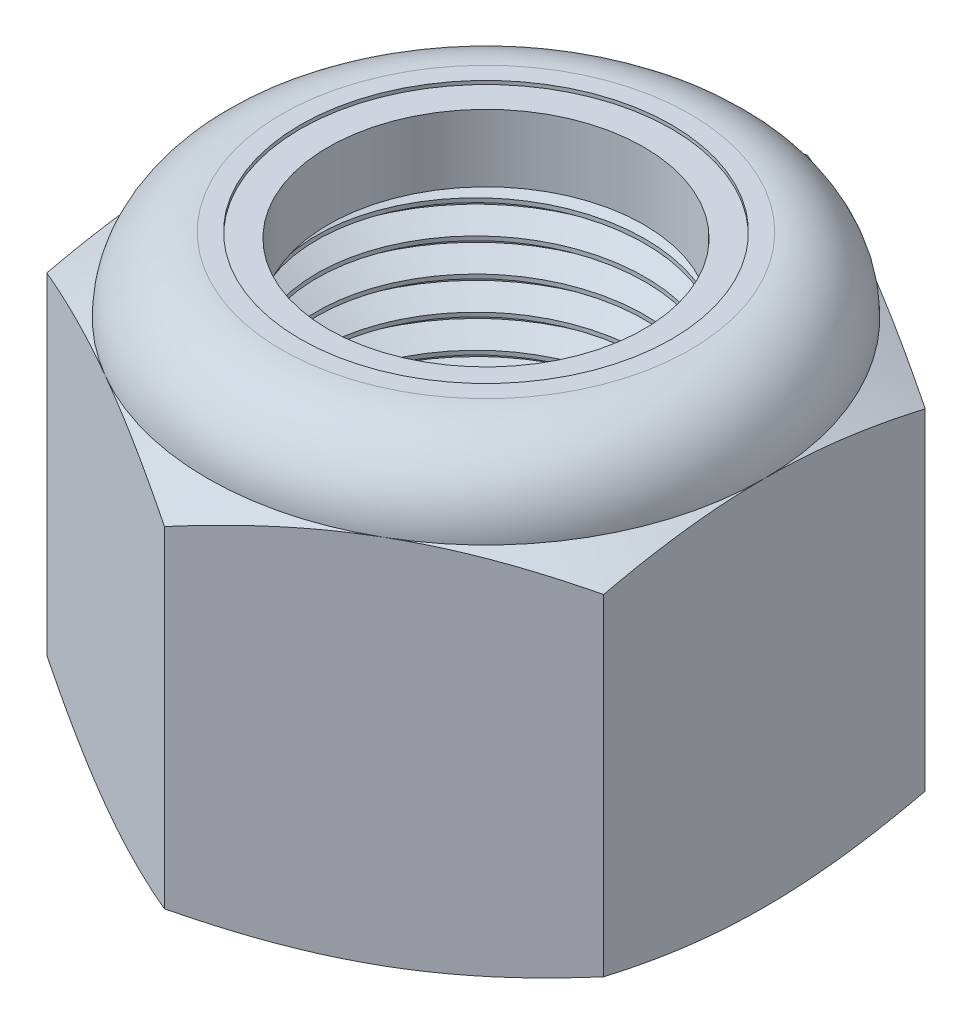
SolidWorks part; units mm, degrees
ref_plane "Front" through (0, 0, 0) normal (0, 0, 1) x (1, 0, 0)
ref_plane "Top" through (0, 0, 0) normal (0, 1, 0) x (1, 0, 0)
ref_plane "Right" through (0, 0, 0) normal (1, 0, 0) x (0, 0, -1)
sketch "Sketch1" plane through (0, 0, 0) normal (1, 0, 0) x (0, 0, -1)
  line L0 (0, 0) -> (0, 19.05) construction
  line L1 (11.9062, 0) -> (-11.9062, 0) construction
  line L2 (-7.9375, 19.05) -> (7.9375, 19.05) construction
  line L3 (7.9375, 19.05) -> (7.9375, 17.6389) construction
  point P9 (-7.9375, 19.05)
  point P10 (7.9375, 19.05)
  point P11 (11.9062, 0)
  dimension "Height" = 19.05
  dimension "Hex Flats" = 23.8125
  dimension "Thread Dia" = 15.875
  dimension "Thread Pitch" = 1.4111
sketch "Sketch13" plane through (0, 0, 0) normal (0, 1, 0) x (1, 0, 0)
  line L1 (0, 13.7482) -> (-11.9063, 6.8741)
  line L2 (-11.9063, 6.8741) -> (-11.9062, -6.8741)
  line L3 (-11.9062, -6.8741) -> (0, -13.7482)
  line L4 (0, -13.7482) -> (11.9063, -6.8741)
  line L5 (11.9063, -6.8741) -> (11.9063, 6.8741)
  line L6 (11.9063, 6.8741) -> (0, 13.7482)
  circle A0 centre (0, 0) radius 11.9062 construction
  circle A1 centre (0, 0) radius 7.9375
  point P11 (0, -7.9375)
  point P13 (0, 7.9375)
extrude "Extrude1" add sketch "Sketch13" along normal up to vertex (19.05 mm away) up to point (0, 19.05, 0)
sketch "Sketch5" plane through (0, 0, 0) normal (1, 0, 0) x (0, 0, -1)
  line L0 (0, 0) -> (11.9062, 0)
  line L1 (11.9062, 0) -> (13.7482, 0.8589)
  line L2 (13.7482, 0.8589) -> (13.7482, 15.0161)
  line L3 (13.7482, 15.0161) -> (11.9062, 15.875)
  line L4 (8.7312, 19.05) -> (8.7312, 20.32)
  line L5 (8.7312, 20.32) -> (15.0182, 20.32)
  line L6 (15.0182, 20.32) -> (15.0182, -1.27)
  line L7 (15.0182, -1.27) -> (0, -1.27)
  line L8 (0, -1.27) -> (0, 0)
  line L9 (11.9062, 15.875) -> (11.9062, 0) construction
  line L12 (13.7482, 19.05) -> (13.7482, 0) construction
  line L13 (13.7482, 9.525) -> (15.0182, 9.525) construction
  line L15 (0, 0) -> (0, 20.32) construction
  line L18 (11.9062, 0) -> (-11.9062, 0) construction
  line L19 (6.8741, 19.05) -> (13.7482, 19.05) construction
  line L20 (0, 20.32) -> (8.7312, 20.32) construction
  line L21 (6.8741, 0) -> (13.7482, 0) construction
  arc A0 (11.9062, 15.875) -> (8.7312, 19.05) centre (8.7312, 15.875) ccw
  dimension "D1" = 25
  dimension "D2" = 1.27
  dimension "D4" = 3.175
revolve "Cut-Revolve3" cut sketch "Sketch5" angle 360 about L15
sketch "Sketch4" plane through (0, 0, 0) normal (1, 0, 0) x (0, 0, -1)
  line L0 (0, 15.875) -> (8.7312, 15.875)
  line L1 (8.7312, 15.875) -> (0, 11.8036)
  line L3 (0, 4.0714) -> (8.7312, 0)
  line L4 (8.7312, 0) -> (0, 0)
  line L5 (0, 0) -> (0, 15.875) construction
  line L10 (0, 0) -> (0, 19.05) construction
  line L11 (0, 4.0714) -> (0, 0)
  line L12 (0, 15.875) -> (0, 11.8036)
  line L13 (10.3111, 15.875) -> (0, 15.875) construction
  dimension "D1" = 25
  dimension "D2" = 17.4625
sketch "Sketch6" plane through (0, 0, 0) normal (1, 0, 0) x (0, 0, -1)
  line L0 (0, 15.875) -> (11.7539, 15.875)
  line L1 (8.7312, 18.8976) -> (4.3656, 18.8976)
  line L2 (0, 20.32) -> (0, 15.875)
  line L3 (4.3656, 20.32) -> (0, 20.32)
  line L4 (0, 20.32) -> (8.7312, 20.32) construction
  line L5 (0, 0) -> (0, 20.32) construction
  line L6 (0, 20.32) -> (0, 0) construction
  line L7 (4.3656, 18.8976) -> (4.3656, 20.32)
  line L8 (8.7312, 19.05) -> (8.7312, 18.8976) construction
  line L9 (4.3656, 18.8976) -> (0, 18.8976) construction
  line L10 (0, 18.8976) -> (0, 11.8036) construction
  arc A0 (11.7539, 15.875) -> (8.7312, 18.8976) centre (8.7312, 15.875) ccw
  arc A1 (11.9062, 15.875) -> (8.7312, 19.05) centre (8.7312, 15.875) ccw construction
  dimension "D1" = 0.1524
revolve "Cut-Revolve4" cut sketch "Sketch6" angle 360 about L6
revolve "Cut-Revolve2" cut sketch "Sketch4" angle 360 about L5
sketch "Sketch7" plane through (0, 0, 0) normal (1, 0, 0) x (0, 0, -1)
  line L0 (6.7469, 15.9512) -> (11.6767, 15.9512)
  line L1 (8.7312, 18.8214) -> (6.7469, 18.8214)
  line L2 (6.7469, 18.8214) -> (6.7469, 15.9512)
  line L3 (6.7469, 15.9512) -> (0, 15.9512) construction
  line L4 (0, 15.9512) -> (0, 18.8214) construction
  line L5 (0, 18.8214) -> (6.7469, 18.8214) construction
  line L6 (6.7469, 15.9512) -> (6.7469, 15.875) construction
  line L7 (0, 15.875) -> (11.7539, 15.875) construction
  line L8 (8.7312, 18.8214) -> (8.7312, 18.8976) construction
  arc A0 (11.6767, 15.9512) -> (8.7312, 18.8214) centre (8.7312, 15.875) ccw
  arc A2 (11.7539, 15.875) -> (8.7312, 18.8976) centre (8.7312, 15.875) ccw construction
  point P15 (6.7469, 18.8214)
  point P18 (-7.7391, 18.8214)
  point P19 (7.7391, 18.8214)
  dimension "D1" = 0.0762
  dimension "D2" = 13.4937
revolve "Revolve2" add sketch "Sketch7" angle 360 about L4
sketch "Sketch2" plane through (0, 0, 0) normal (1, 0, 0) x (0, 0, -1)
  line L0 (-7.9375, 0) -> (-7.9375, 15.875) construction
  line L1 (0, 0) -> (7.9375, 0)
  line L2 (0, 0) -> (0, 15.875)
  line L3 (0, 15.875) -> (7.9375, 15.875)
  line L4 (7.9375, 0) -> (7.9375, 15.875)
  line L6 (10.3111, 15.875) -> (11.9062, 15.875) construction
  line L7 (0, -7.9375) -> (0, 0) construction
revolve "Revolve1" add sketch "Sketch2" angle 360 about L7
sketch "Sketch9" plane through (0, 0, 0) normal (1, 0, 0) x (0, 0, -1)
  line L0 (8.0903, 17.1979) -> (8.0903, 15.7868) construction
  line L1 (8.0903, 15.7868) -> (6.8682, 16.4924) construction
  line L2 (6.8682, 16.4924) -> (8.0903, 17.1979) construction
  line L3 (7.021, 16.5806) -> (7.021, 16.4042) construction
  line L4 (7.9375, 17.1097) -> (7.9375, 15.875) construction
  line L5 (6.8682, 16.4924) -> (7.021, 16.4924) construction
  line L6 (7.9375, 16.4924) -> (8.0903, 16.4924) construction
  line L7 (8.0139, 16.4924) -> (8.0139, 17.1538) construction
  line L8 (8.0903, 15.7868) -> (8.0139, 17.1538)
  line L9 (8.0139, 17.1538) -> (7.021, 16.5806)
  line L10 (7.021, 16.5806) -> (7.021, 16.4042)
  line L11 (7.021, 16.4042) -> (8.0903, 15.7868)
  dimension "D1" = 1.4111
  dimension "D2" = 0.1764
sketch "Sketch10" plane through (0, 15.875, 0) normal (0, 1, 0) x (1, 0, 0)
  circle A1 centre (0, 0) radius 7.9375
  circle A2 centre (0, 0) radius 7.9375
  dimension "D1" = 0
curve "Helix/Spiral1" pitch 1.4111 height 20.4611 turns 14.5
sweep "Cut-Sweep1" cut profiles "Sketch9" path "Helix/Spiral1"
sketch "Sketch11" plane through (0, 0, 0) normal (1, 0, 0) x (0, 0, -1)
  line L0 (0, 0) -> (0, 19.05) construction
  line L1 (11.9062, 0) -> (-11.9062, 0) construction
  line L4 (0, 19.05) -> (0, 0) construction
  line L5 (0, 9.525) -> (7.9375, 9.525) construction
  line L6 (0, 0) -> (8.7313, 0)
  line L7 (0, 4.0714) -> (0, 0)
  line L8 (8.7313, 0) -> (0, 4.0714)
  dimension "D1" = 17.4625
  dimension "D2" = 25
revolve "Revolve3" add sketch "Sketch11" angle 360 about L4
sketch "Sketch12" plane through (0, 0, 0) normal (1, 0, 0) x (0, 0, -1)
  line L0 (8.7312, 15.875) -> (0, 15.875)
  line L1 (0, 15.875) -> (0, 0)
  line L2 (0, 0) -> (8.7312, 0)
  line L3 (11.9062, 0) -> (-11.9062, 0) construction
  line L4 (8.7312, 0) -> (8.7312, 15.875)
  line L5 (-8.7312, 0) -> (8.7312, 0) construction
revolve "Revolve4" add sketch "Sketch12" angle 360 about L0
combine bodies "Combine1" bodies to combine 136 133
equation "\"D4@Sketch5\" = \"Height@Sketch1\" / 6"
equation "\"D1@Sketch9\" = \"Thread Pitch@Sketch1\""
equation "\"D2@Sketch9\" = \"Thread Pitch@Sketch1\" / 8"
equation "\"D4@Helix/Spiral1\" = \"Thread Pitch@Sketch1\""
equation "\"D3@Helix/Spiral1\" = \"Thread Pitch@Sketch1\" + \"Height@Sketch1\""
equation "\"D2@Sketch4\" = \"Thread Dia@Sketch1\" * 1.1"
equation "\"D1@Sketch11\" = \"Thread Dia@Sketch1\" * 1.1"
equation "\"D2@Sketch7\" = \"Thread Dia@Sketch1\" * .85"
